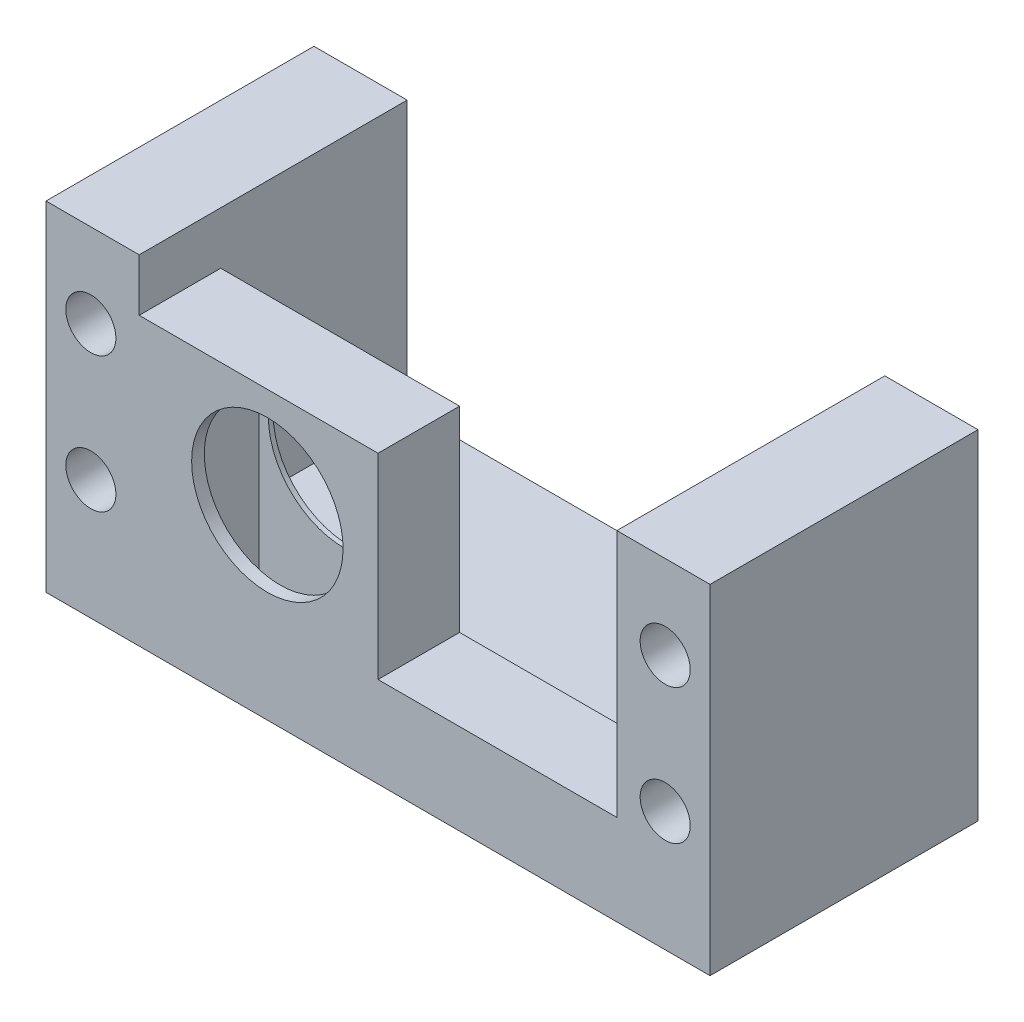
SolidWorks part; units mm, degrees
ref_plane "Спереди" through (0, 0, 0) normal (0, 0, 1) x (1, 0, 0)
ref_plane "Сверху" through (0, 0, 0) normal (0, 1, 0) x (1, 0, 0)
ref_plane "Справа" through (0, 0, 0) normal (1, 0, 0) x (0, 0, -1)
sketch "Эскиз1" plane through (0, 0, 0) normal (0, 0, 1) x (1, 0, 0)
  line L2 (-59.1906, -40.1769) -> (-59.1906, -15.0857)
  line L3 (-59.1906, -15.0857) -> (-51.1906, -15.0857)
  line L4 (-2.1906, -38.0857) -> (-2.1906, -15.0857)
  line L8 (-2.1906, -15.0857) -> (-10.1906, -15.0857)
  line L9 (-10.1906, -15.0857) -> (-10.1906, -38.0857)
  line L10 (-51.1906, -15.0857) -> (-51.1906, -38.0857)
  line L11 (-51.1906, -38.0857) -> (-10.1906, -38.0857)
  line L12 (-59.1906, -40.1769) -> (-59.1906, -44.1769)
  line L13 (-59.1906, -44.1769) -> (-2.1906, -44.1769)
  line L14 (-2.1906, -44.1769) -> (-2.1906, -38.0857)
  point P0 (0, 0)
extrude "Бобышка-Вытянуть1" add sketch "Эскиз1" along normal blind 23
sketch "Эскиз3" plane through (-59.1906, 0, 0) normal (-1, 0, 0) x (0, 0, 1)
  line L5 (0, -15.0857) -> (0, -44.1769) construction
  line L6 (15, -15.0857) -> (0, -15.0857) construction
  line L7 (15, -15.0857) -> (15, -38.2478) construction
  line L8 (15, -38.2478) -> (0, -38.2478) construction
  line L9 (0, -15.0857) -> (0, -38.2478) construction
sketch "Эскиз15" plane through (0, 0, 23) normal (0, 0, 1) x (1, 0, 0)
  line L3 (-40.1906, -22.6769) -> (-40.1906, -28.1769) construction
  point P0 (0, 0)
sketch "Эскиз5" plane through (0, 0, 23) normal (0, 0, 1) x (1, 0, 0)
  line L0 (-51.1906, -38.0857) -> (-51.1906, -15.0857) construction
  line L1 (-10.1906, -28.0857) -> (-24.1906, -28.0857) construction
  line L6 (-30.6906, -18.0857) -> (-30.6906, -34.9839) construction
  line L11 (-51.1906, -28.0857) -> (-37.1906, -28.0857) construction
  line L12 (-10.1906, -38.0857) -> (-51.1906, -38.0857) construction
  line L13 (-10.1906, -38.0857) -> (-10.1906, -18.0857) construction
  line L14 (-10.1906, -18.0857) -> (-51.1906, -18.0857) construction
  line L15 (-51.1906, -38.0857) -> (-51.1906, -18.0857) construction
  line L16 (-21.1906, -34.9839) -> (-51.1906, -34.9839) construction
  line L18 (-21.1906, -19.5857) -> (-51.1906, -19.5857)
  line L19 (-51.1906, -34.9839) -> (-51.1906, -19.5857)
  line L20 (-21.1906, -19.5857) -> (-10.1906, -19.5857)
  line L22 (-21.1906, -34.9839) -> (-10.1906, -34.9839) construction
  line L23 (-10.1906, -19.5857) -> (-10.1906, -34.9839)
  line L24 (-10.1906, -38.0857) -> (-51.1906, -38.0857)
  line L25 (-51.1906, -38.0857) -> (-51.1906, -34.9839)
  line L26 (-10.1906, -38.0857) -> (-10.1906, -34.9839)
  circle A5 centre (-21.1906, -28.0857) radius 2.7
  circle A6 centre (-40.1906, -28.1769) radius 6.5
  point P23 (-40.1906, -28.0857)
  point P24 (-40.1906, -28.0857)
  point P25 (0, 0)
  point P26 (-40.1906, -28.1769)
  point P27 (0, 0)
  point P28 (0, 0)
extrude "Бобышка-Вытянуть6" add sketch "Эскиз5" against normal blind 7
sketch "Эскиз6" plane through (0, 0, 23) normal (0, 0, 1) x (1, 0, 0)
  line L0 (-51.1906, -19.5857) -> (-51.1906, -15.0857) construction
  line L3 (-10.1906, -18.0857) -> (-51.1906, -18.0857)
  line L4 (-51.1906, -38.0857) -> (-51.1906, -18.0857)
  line L5 (-2.1906, -38.0857) -> (-59.1906, -38.0857) construction
  line L6 (-2.1906, -44.1769) -> (-2.1906, -15.0857) construction
  line L7 (-6.0406, -38.0857) -> (-6.0406, -29.5857) construction
  line L8 (-59.1906, -15.0857) -> (-59.1906, -44.1769) construction
  line L9 (-10.1906, -18.0857) -> (-2.1906, -18.0857) construction
  line L10 (-6.0406, -18.0857) -> (-6.0406, -26.5857) construction
  line L11 (-6.0406, -22.2857) -> (-10.1906, -22.2857) construction
  line L12 (-30.6906, -38.0857) -> (-30.6906, -18.0857) construction
  line L13 (-10.1906, -18.0857) -> (-10.1906, -38.0857) construction
  line L14 (-6.0406, -33.8857) -> (-10.1906, -33.8857) construction
  circle A1 centre (-6.0406, -33.8857) radius 2.15
  circle A3 centre (-6.0406, -22.2857) radius 2.15
  circle A4 centre (-55.3406, -22.2857) radius 2.15
  circle A5 centre (-55.3406, -33.8857) radius 2.15
extrude "Вырез-Вытянуть2" cut sketch "Эскиз6" against normal through all contours A1 | A3 | A5 | A4 region at (-6.0406, -33.8857, 23) region at (-6.0406, -22.2857, 23) region at (-55.3406, -22.2857, 23) region at (-55.3406, -33.8857, 23)
sketch "Эскиз8" plane through (0, 0, 23) normal (0, 0, 1) x (1, 0, 0)
  line L1 (-10.1906, -19.5857) -> (-30.6906, -19.5857)
  line L2 (-10.1906, -19.5857) -> (-10.1906, -36.4088)
  line L3 (-10.1906, -36.4088) -> (-30.6906, -36.4088)
  line L4 (-30.6906, -19.5857) -> (-30.6906, -36.4088)
extrude "Вырез-Вытянуть4" cut sketch "Эскиз8" against normal up to surface (7 mm away) up to face at (-46.6906, -28.1769, 16)
sketch "Эскиз14" plane through (0, -44.1769, 0) normal (0, -1, 0) x (-1, 0, 0)
  line L0 (40.2278, -23) -> (40.2278, -19.1629) construction
  line L1 (59.1906, -23) -> (2.1906, -23) construction
  line L3 (32.9778, -21.9129) -> (47.4778, -21.9129)
  line L4 (32.9778, -21.9129) -> (32.9778, -16.4129)
  line L5 (32.9778, -16.4129) -> (47.4778, -16.4129)
  line L6 (47.4778, -21.9129) -> (47.4778, -16.4129)
  line L7 (32.9778, -21.9129) -> (47.4778, -16.4129) construction
  line L8 (32.9778, -16.4129) -> (47.4778, -21.9129) construction
extrude "Вырез-Вытянуть7" cut sketch "Эскиз14" against normal blind 22.74
